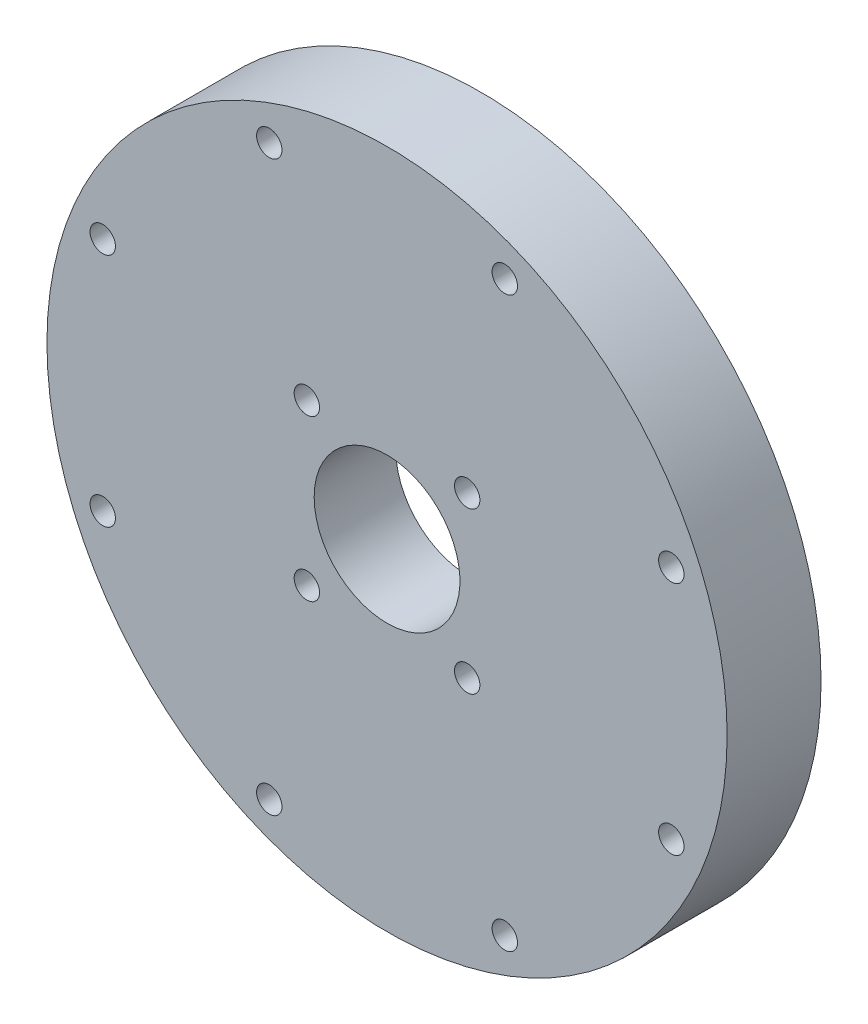
SolidWorks part; units mm, degrees
material "6061-T6 (SS)"
ref_plane "Front Plane" through (0, 0, 0) normal (0, 0, 1) x (1, 0, 0)
ref_plane "Top Plane" through (0, 0, 0) normal (0, 1, 0) x (1, 0, 0)
ref_plane "Right Plane" through (0, 0, 0) normal (1, 0, 0) x (0, 0, -1)
curve "Volute Curve"
  spline degree 3 poles (34.2618, 0, 0) (34.2648, 0.0718, 0) (34.2707, 0.2156, 0) (34.2778, 0.4312, 0) (34.2837, 0.647, 0) (34.2882, 0.8628, 0) (34.2914, 1.0787, 0) (34.2932, 1.2947, 0) (34.2937, 1.5108, 0) (34.2929, 1.7269, 0) (34.2907, 1.9431, 0) (34.2871, 2.1593, 0) (34.2822, 2.3756, 0) (34.2759, 2.5919, 0) (34.2683, 2.8082, 0) (34.2593, 3.0245, 0) (34.2489, 3.2407, 0) (34.2372, 3.457, 0) (34.2242, 3.6733, 0) (34.2098, 3.8895, 0) (34.194, 4.1058, 0) (34.1768, 4.3219, 0) (34.1583, 4.538, 0) (34.1385, 4.7541, 0) (34.1173, 4.9701, 0) (34.0947, 5.186, 0) (34.0708, 5.4018, 0) (34.0454, 5.6175, 0) (34.0188, 5.8331, 0) (33.9908, 6.0486, 0) (33.9614, 6.264, 0) (33.9306, 6.4793, 0) (33.8985, 6.6944, 0) (33.8651, 6.9094, 0) (33.8303, 7.1242, 0) (33.7941, 7.3388, 0) (33.7566, 7.5533, 0) (33.7177, 7.7676, 0) (33.6774, 7.9817, 0) (33.6358, 8.1956, 0) (33.5929, 8.4093, 0) (33.5486, 8.6228, 0) (33.5029, 8.8361, 0) (33.4559, 9.0491, 0) (33.4076, 9.2619, 0) (33.3579, 9.4745, 0) (33.3068, 9.6868, 0) (33.2544, 9.8988, 0) (33.2006, 10.1105, 0) (33.1456, 10.322, 0) (33.0891, 10.5332, 0) (33.0313, 10.744, 0) (32.9722, 10.9546, 0) (32.9118, 11.1648, 0) (32.85, 11.3748, 0) (32.7869, 11.5843, 0) (32.7224, 11.7936, 0) (32.6566, 12.0025, 0) (32.5895, 12.211, 0) (32.521, 12.4192, 0) (32.4513, 12.627, 0) (32.3802, 12.8344, 0) (32.3077, 13.0414, 0) (32.234, 13.248, 0) (32.1589, 13.4542, 0) (32.0826, 13.6599, 0) (32.0049, 13.8653, 0) (31.9259, 14.0702, 0) (31.8456, 14.2747, 0) (31.764, 14.4787, 0) (31.6811, 14.6823, 0) (31.5968, 14.8854, 0) (31.5113, 15.088, 0) (31.4245, 15.2901, 0) (31.3364, 15.4917, 0) (31.247, 15.6929, 0) (31.1563, 15.8935, 0) (31.0644, 16.0936, 0) (30.9711, 16.2932, 0) (30.8766, 16.4922, 0) (30.7808, 16.6907, 0) (30.6837, 16.8886, 0) (30.5854, 17.086, 0) (30.4858, 17.2829, 0) (30.3849, 17.4791, 0) (30.2828, 17.6748, 0) (30.1794, 17.8698, 0) (30.0747, 18.0643, 0) (29.9688, 18.2582, 0) (29.8617, 18.4514, 0) (29.7533, 18.644, 0) (29.6437, 18.836, 0) (29.5328, 19.0274, 0) (29.4208, 19.2181, 0) (29.3074, 19.4081, 0) (29.1929, 19.5975, 0) (29.0771, 19.7862, 0) (28.9601, 19.9742, 0) (28.842, 20.1616, 0) (28.7226, 20.3482, 0) (28.602, 20.5342, 0) (28.4801, 20.7194, 0) (28.3571, 20.904, 0) (28.233, 21.0877, 0) (28.1076, 21.2708, 0) (27.981, 21.4531, 0) (27.8533, 21.6347, 0) (27.7243, 21.8155, 0) (27.5942, 21.9956, 0) (27.463, 22.1748, 0) (27.3306, 22.3533, 0) (27.197, 22.531, 0) (27.0623, 22.708, 0) (26.9264, 22.8841, 0) (26.7894, 23.0594, 0) (26.6512, 23.2339, 0) (26.5119, 23.4075, 0) (26.3715, 23.5804, 0) (26.23, 23.7524, 0) (26.0873, 23.9235, 0) (25.9435, 24.0938, 0) (25.7987, 24.2632, 0) (25.6527, 24.4318, 0) (25.5056, 24.5995, 0) (25.3574, 24.7663, 0) (25.2082, 24.9322, 0) (25.0578, 25.0973, 0) (24.9064, 25.2614, 0) (24.7539, 25.4246, 0) (24.6003, 25.5869, 0) (24.4457, 25.7483, 0) (24.29, 25.9087, 0) (24.1333, 26.0682, 0) (23.9755, 26.2268, 0) (23.8167, 26.3844, 0) (23.6569, 26.541, 0) (23.496, 26.6967, 0) (23.3341, 26.8514, 0) (23.1712, 27.0051, 0) (23.0073, 27.1579, 0) (22.8424, 27.3096, 0) (22.6765, 27.4604, 0) (22.5096, 27.6101, 0) (22.3417, 27.7589, 0) (22.1728, 27.9066, 0) (22.003, 28.0533, 0) (21.8322, 28.199, 0) (21.6604, 28.3436, 0) (21.4877, 28.4872, 0) (21.314, 28.6297, 0) (21.1394, 28.7712, 0) (20.9639, 28.9116, 0) (20.7874, 29.051, 0) (20.61, 29.1892, 0) (20.4317, 29.3264, 0) (20.2524, 29.4626, 0) (20.0723, 29.5976, 0) (19.8913, 29.7315, 0) (19.7094, 29.8643, 0) (19.5266, 29.996, 0) (19.3429, 30.1266, 0) (19.1584, 30.2561, 0) (18.973, 30.3844, 0) (18.7867, 30.5116, 0) (18.5996, 30.6377, 0) (18.4117, 30.7626, 0) (18.2229, 30.8864, 0) (18.0333, 31.009, 0) (17.8429, 31.1304, 0) (17.6516, 31.2507, 0) (17.4596, 31.3698, 0) (17.2667, 31.4878, 0) (17.0731, 31.6045, 0) (16.8786, 31.7201, 0) (16.6834, 31.8344, 0) (16.4875, 31.9476, 0) (16.2907, 32.0596, 0) (16.0932, 32.1703, 0) (15.895, 32.2799, 0) (15.696, 32.3882, 0) (15.4963, 32.4953, 0) (15.2959, 32.6012, 0) (15.0947, 32.7058, 0) (14.8929, 32.8092, 0) (14.6903, 32.9114, 0) (14.487, 33.0123, 0) (14.2831, 33.1119, 0) (14.0784, 33.2103, 0) (13.8731, 33.3075, 0) (13.6672, 33.4033, 0) (13.4606, 33.4979, 0) (13.2533, 33.5912, 0) (13.0454, 33.6833, 0) (12.8368, 33.774, 0) (12.6277, 33.8635, 0) (12.4179, 33.9517, 0) (12.2075, 34.0385, 0) (11.9965, 34.1241, 0) (11.7849, 34.2084, 0) (11.5727, 34.2913, 0) (11.36, 34.373, 0) (11.1467, 34.4533, 0) (10.9328, 34.5323, 0) (10.7183, 34.61, 0) (10.5034, 34.6863, 0) (10.2879, 34.7613, 0) (10.0718, 34.835, 0) (9.8553, 34.9074, 0) (9.6382, 34.9783, 0) (9.4206, 35.048, 0) (9.2025, 35.1163, 0) (8.984, 35.1832, 0) (8.765, 35.2488, 0) (8.5455, 35.313, 0) (8.3255, 35.3759, 0) (8.1051, 35.4374, 0) (7.8842, 35.4975, 0) (7.6629, 35.5562, 0) (7.4412, 35.6136, 0) (7.2191, 35.6696, 0) (6.9965, 35.7242, 0) (6.7736, 35.7774, 0) (6.5503, 35.8292, 0) (6.3265, 35.8796, 0) (6.1024, 35.9287, 0) (5.878, 35.9763, 0) (5.6532, 36.0225, 0) (5.428, 36.0674, 0) (5.2025, 36.1108, 0) (4.9766, 36.1528, 0) (4.7505, 36.1934, 0) (4.524, 36.2326, 0) (4.2972, 36.2704, 0) (4.0701, 36.3067, 0) (3.8428, 36.3417, 0) (3.6151, 36.3752, 0) (3.3872, 36.4073, 0) (3.159, 36.438, 0) (2.9306, 36.4672, 0) (2.7019, 36.495, 0) (2.473, 36.5214, 0) (2.2439, 36.5463, 0) (2.0146, 36.5699, 0) (1.785, 36.5919, 0) (1.5553, 36.6126, 0) (1.3253, 36.6318, 0) (1.0952, 36.6495, 0) (0.8649, 36.6658, 0) (0.6345, 36.6807, 0) (0.4039, 36.6941, 0) (0.1731, 36.706, 0) (-0.0577, 36.7166, 0) (-0.2887, 36.7256, 0) (-0.5199, 36.7332, 0) (-0.7511, 36.7394, 0) (-0.9824, 36.7441, 0) (-1.2138, 36.7474, 0) (-1.4453, 36.7492, 0) (-1.6769, 36.7495, 0) (-1.9085, 36.7484, 0) (-2.1402, 36.7458, 0) (-2.3719, 36.7418, 0) (-2.6037, 36.7363, 0) (-2.8355, 36.7293, 0) (-3.0673, 36.7209, 0) (-3.2991, 36.711, 0) (-3.5309, 36.6997, 0) (-3.7627, 36.6869, 0) (-3.9944, 36.6726, 0) (-4.2262, 36.6569, 0) (-4.4579, 36.6397, 0) (-4.6895, 36.6211, 0) (-4.9211, 36.6009, 0) (-5.1526, 36.5794, 0) (-5.3841, 36.5563, 0) (-5.6154, 36.5318, 0) (-5.8467, 36.5059, 0) (-6.0779, 36.4784, 0) (-6.3089, 36.4495, 0) (-6.5399, 36.4192, 0) (-6.7706, 36.3874, 0) (-7.0013, 36.3541, 0) (-7.2318, 36.3194, 0) (-7.4621, 36.2832, 0) (-7.6923, 36.2455, 0) (-7.9223, 36.2064, 0) (-8.1521, 36.1658, 0) (-8.3817, 36.1238, 0) (-8.6111, 36.0803, 0) (-8.8403, 36.0354, 0) (-9.0693, 35.989, 0) (-9.298, 35.9411, 0) (-9.5265, 35.8918, 0) (-9.7548, 35.8411, 0) (-9.9827, 35.7889, 0) (-10.2105, 35.7352, 0) (-10.4379, 35.6802, 0) (-10.665, 35.6236, 0) (-10.8919, 35.5656, 0) (-11.1184, 35.5062, 0) (-11.3446, 35.4453, 0) (-11.5705, 35.383, 0) (-11.7961, 35.3193, 0) (-12.0213, 35.2541, 0) (-12.2461, 35.1875, 0) (-12.4706, 35.1194, 0) (-12.6948, 35.0499, 0) (-12.9185, 34.979, 0) (-13.1419, 34.9067, 0) (-13.3648, 34.8329, 0) (-13.5874, 34.7578, 0) (-13.8095, 34.6812, 0) (-14.0312, 34.6031, 0) (-14.2525, 34.5237, 0) (-14.4734, 34.4429, 0) (-14.6937, 34.3606, 0) (-14.9137, 34.2769, 0) (-15.1331, 34.1918, 0) (-15.3521, 34.1054, 0) (-15.5706, 34.0175, 0) (-15.7885, 33.9282, 0) (-16.006, 33.8375, 0) (-16.223, 33.7455, 0) (-16.4394, 33.652, 0) (-16.6553, 33.5572, 0) (-16.8707, 33.461, 0) (-17.0855, 33.3634, 0) (-17.2997, 33.2644, 0) (-17.5134, 33.164, 0) (-17.7265, 33.0623, 0) (-17.939, 32.9592, 0) (-18.151, 32.8548, 0) (-18.3623, 32.7489, 0) (-18.573, 32.6418, 0) (-18.7831, 32.5332, 0) (-18.9925, 32.4234, 0) (-19.2014, 32.3121, 0) (-19.4095, 32.1996, 0) (-19.6171, 32.0857, 0) (-19.8239, 31.9704, 0) (-20.0301, 31.8538, 0) (-20.2356, 31.7359, 0) (-20.4404, 31.6167, 0) (-20.6445, 31.4962, 0) (-20.8479, 31.3743, 0) (-21.0506, 31.2511, 0) (-21.2526, 31.1267, 0) (-21.4538, 31.0009, 0) (-21.6543, 30.8738, 0) (-21.854, 30.7454, 0) (-22.053, 30.6158, 0) (-22.2512, 30.4848, 0) (-22.4487, 30.3526, 0) (-22.6453, 30.2191, 0) (-22.8412, 30.0843, 0) (-23.0363, 29.9482, 0) (-23.2305, 29.8109, 0) (-23.424, 29.6723, 0) (-23.6166, 29.5325, 0) (-23.8084, 29.3915, 0) (-23.9994, 29.2491, 0) (-24.1895, 29.1056, 0) (-24.3787, 28.9608, 0) (-24.5671, 28.8148, 0) (-24.7546, 28.6676, 0) (-24.9413, 28.5191, 0) (-25.127, 28.3694, 0) (-25.3119, 28.2186, 0) (-25.4958, 28.0665, 0) (-25.6789, 27.9132, 0) (-25.861, 27.7587, 0) (-26.0422, 27.6031, 0) (-26.2224, 27.4463, 0) (-26.4018, 27.2882, 0) (-26.5801, 27.1291, 0) (-26.7576, 26.9687, 0) (-26.934, 26.8072, 0) (-27.1095, 26.6446, 0) (-27.284, 26.4808, 0) (-27.4575, 26.3159, 0) (-27.63, 26.1498, 0) (-27.8015, 25.9826, 0) (-27.972, 25.8143, 0) (-28.1415, 25.6448, 0) (-28.31, 25.4743, 0) (-28.4774, 25.3027, 0) (-28.6438, 25.1299, 0) (-28.8092, 24.9561, 0) (-28.9735, 24.7811, 0) (-29.1367, 24.6051, 0) (-29.2989, 24.4281, 0) (-29.46, 24.2499, 0) (-29.62, 24.0707, 0) (-29.7789, 23.8905, 0) (-29.9368, 23.7092, 0) (-30.0935, 23.5268, 0) (-30.2491, 23.3435, 0) (-30.4036, 23.1591, 0) (-30.557, 22.9737, 0) (-30.7093, 22.7872, 0) (-30.8604, 22.5998, 0) (-31.0104, 22.4114, 0) (-31.1592, 22.2219, 0) (-31.3069, 22.0315, 0) (-31.4534, 21.8402, 0) (-31.5988, 21.6478, 0) (-31.7429, 21.4545, 0) (-31.8859, 21.2602, 0) (-32.0277, 21.065, 0) (-32.1684, 20.8688, 0) (-32.3078, 20.6717, 0) (-32.446, 20.4737, 0) (-32.583, 20.2747, 0) (-32.7188, 20.0748, 0) (-32.8533, 19.8741, 0) (-32.9866, 19.6724, 0) (-33.1187, 19.4698, 0) (-33.2496, 19.2664, 0) (-33.3792, 19.0621, 0) (-33.5075, 18.8569, 0) (-33.6346, 18.6509, 0) (-33.7604, 18.444, 0) (-33.885, 18.2362, 0) (-34.0082, 18.0276, 0) (-34.1302, 17.8182, 0) (-34.2509, 17.608, 0) (-34.3703, 17.397, 0) (-34.4884, 17.1851, 0) (-34.6052, 16.9725, 0) (-34.7207, 16.7591, 0) (-34.8349, 16.5449, 0) (-34.9478, 16.3299, 0) (-35.0593, 16.1141, 0) (-35.1695, 15.8976, 0) (-35.2784, 15.6804, 0) (-35.3859, 15.4624, 0) (-35.4921, 15.2436, 0) (-35.597, 15.0242, 0) (-35.7004, 14.804, 0) (-35.8026, 14.5832, 0) (-35.9033, 14.3616, 0) (-36.0027, 14.1393, 0) (-36.1007, 13.9164, 0) (-36.1973, 13.6928, 0) (-36.2926, 13.4685, 0) (-36.3864, 13.2436, 0) (-36.4789, 13.018, 0) (-36.57, 12.7918, 0) (-36.6596, 12.5649, 0) (-36.7479, 12.3374, 0) (-36.8348, 12.1094, 0) (-36.9202, 11.8807, 0) (-37.0042, 11.6514, 0) (-37.0868, 11.4215, 0) (-37.168, 11.1911, 0) (-37.2477, 10.96, 0) (-37.326, 10.7285, 0) (-37.4029, 10.4963, 0) (-37.4783, 10.2637, 0) (-37.5523, 10.0305, 0) (-37.6248, 9.7967, 0) (-37.6959, 9.5625, 0) (-37.7655, 9.3277, 0) (-37.8337, 9.0925, 0) (-37.9004, 8.8568, 0) (-37.9656, 8.6205, 0) (-38.0293, 8.3839, 0) (-38.0916, 8.1467, 0) (-38.1524, 7.9091, 0) (-38.2117, 7.6711, 0) (-38.2696, 7.4326, 0) (-38.3259, 7.1937, 0) (-38.3808, 6.9544, 0) (-38.4342, 6.7147, 0) (-38.486, 6.4746, 0) (-38.5364, 6.2341, 0) (-38.5853, 5.9932, 0) (-38.6326, 5.7519, 0) (-38.6785, 5.5103, 0) (-38.7229, 5.2684, 0) (-38.7657, 5.0261, 0) (-38.807, 4.7835, 0) (-38.8468, 4.5405, 0) (-38.8851, 4.2973, 0) (-38.9219, 4.0537, 0) (-38.9571, 3.8099, 0) (-38.9908, 3.5657, 0) (-39.023, 3.3213, 0) (-39.0537, 3.0767, 0) (-39.0828, 2.8317, 0) (-39.1104, 2.5866, 0) (-39.1364, 2.3412, 0) (-39.1609, 2.0955, 0) (-39.1839, 1.8497, 0) (-39.2053, 1.6037, 0) (-39.2252, 1.3574, 0) (-39.2435, 1.111, 0) (-39.2603, 0.8644, 0) (-39.2756, 0.6176, 0) (-39.2893, 0.3707, 0) (-39.3014, 0.1236, 0) (-39.312, -0.1236, 0) (-39.321, -0.371, 0) (-39.3285, -0.6185, 0) (-39.3344, -0.866, 0) (-39.3388, -1.1137, 0) (-39.3416, -1.3615, 0) (-39.3428, -1.6093, 0) (-39.3425, -1.8572, 0) (-39.3406, -2.1052, 0) (-39.3372, -2.3532, 0) (-39.3322, -2.6013, 0) (-39.3257, -2.8494, 0) (-39.3175, -3.0975, 0) (-39.3078, -3.3456, 0) (-39.2966, -3.5937, 0) (-39.2838, -3.8418, 0) (-39.2694, -4.0899, 0) (-39.2534, -4.338, 0) (-39.2359, -4.586, 0) (-39.2168, -4.834, 0) (-39.1962, -5.0819, 0) (-39.174, -5.3298, 0) (-39.1502, -5.5776, 0) (-39.1248, -5.8252, 0) (-39.0979, -6.0728, 0) (-39.0694, -6.3203, 0) (-39.0394, -6.5677, 0) (-39.0078, -6.8149, 0) (-38.9746, -7.062, 0) (-38.9399, -7.309, 0) (-38.9036, -7.5558, 0) (-38.8657, -7.8024, 0) (-38.8263, -8.0488, 0) (-38.7853, -8.2951, 0) (-38.7427, -8.5411, 0) (-38.6986, -8.787, 0) (-38.653, -9.0326, 0) (-38.6057, -9.2781, 0) (-38.557, -9.5232, 0) (-38.5066, -9.7682, 0) (-38.4547, -10.0128, 0) (-38.4013, -10.2572, 0) (-38.3463, -10.5014, 0) (-38.2897, -10.7452, 0) (-38.2316, -10.9888, 0) (-38.172, -11.232, 0) (-38.1108, -11.475, 0) (-38.048, -11.7176, 0) (-37.9838, -11.9598, 0) (-37.9179, -12.2018, 0) (-37.8506, -12.4433, 0) (-37.7817, -12.6845, 0) (-37.7112, -12.9254, 0) (-37.6393, -13.1658, 0) (-37.5658, -13.4059, 0) (-37.4907, -13.6455, 0) (-37.4142, -13.8848, 0) (-37.3361, -14.1236, 0) (-37.2565, -14.362, 0) (-37.1753, -14.5999, 0) (-37.0927, -14.8374, 0) (-37.0085, -15.0744, 0) (-36.9228, -15.311, 0) (-36.8357, -15.547, 0) (-36.747, -15.7826, 0) (-36.6568, -16.0177, 0) (-36.5651, -16.2523, 0) (-36.4719, -16.4863, 0) (-36.3772, -16.7199, 0) (-36.281, -16.9528, 0) (-36.1833, -17.1853, 0) (-36.0841, -17.4172, 0) (-35.9834, -17.6485, 0) (-35.8813, -17.8792, 0) (-35.7777, -18.1094, 0) (-35.6726, -18.3389, 0) (-35.566, -18.5679, 0) (-35.458, -18.7962, 0) (-35.3485, -19.0239, 0) (-35.2376, -19.251, 0) (-35.1251, -19.4774, 0) (-35.0113, -19.7032, 0) (-34.896, -19.9283, 0) (-34.7792, -20.1528, 0) (-34.661, -20.3765, 0) (-34.5414, -20.5996, 0) (-34.4203, -20.822, 0) (-34.2978, -21.0437, 0) (-34.1738, -21.2646, 0) (-34.0485, -21.4849, 0) (-33.9217, -21.7044, 0) (-33.7935, -21.9231, 0) (-33.6639, -22.1411, 0) (-33.5329, -22.3584, 0) (-33.4005, -22.5748, 0) (-33.2667, -22.7905, 0) (-33.1315, -23.0054, 0) (-32.995, -23.2195, 0) (-32.857, -23.4328, 0) (-32.7177, -23.6453, 0) (-32.577, -23.8569, 0) (-32.4349, -24.0677, 0) (-32.2915, -24.2777, 0) (-32.1467, -24.4868, 0) (-32.0006, -24.6951, 0) (-31.8531, -24.9025, 0) (-31.7042, -25.109, 0) (-31.5541, -25.3146, 0) (-31.4026, -25.5194, 0) (-31.2497, -25.7232, 0) (-31.0956, -25.9261, 0) (-30.9401, -26.1281, 0) (-30.7833, -26.3292, 0) (-30.6253, -26.5293, 0) (-30.4659, -26.7285, 0) (-30.3052, -26.9267, 0) (-30.1433, -27.124, 0) (-29.98, -27.3203, 0) (-29.8155, -27.5156, 0) (-29.6497, -27.7099, 0) (-29.4827, -27.9032, 0) (-29.3144, -28.0956, 0) (-29.1448, -28.2869, 0) (-28.974, -28.4772, 0) (-28.8019, -28.6664, 0) (-28.6287, -28.8546, 0) (-28.4542, -29.0418, 0) (-28.2784, -29.2279, 0) (-28.1015, -29.413, 0) (-27.9233, -29.597, 0) (-27.744, -29.7799, 0) (-27.5634, -29.9618, 0) (-27.3817, -30.1425, 0) (-27.1987, -30.3221, 0) (-27.0146, -30.5007, 0) (-26.8294, -30.6781, 0) (-26.6429, -30.8544, 0) (-26.4554, -31.0296, 0) (-26.2666, -31.2036, 0) (-26.0767, -31.3765, 0) (-25.8857, -31.5482, 0) (-25.6936, -31.7188, 0) (-25.5003, -31.8882, 0) (-25.306, -32.0564, 0) (-25.1105, -32.2234, 0) (-24.9139, -32.3893, 0) (-24.7162, -32.5539, 0) (-24.5175, -32.7174, 0) (-24.3176, -32.8796, 0) (-24.1167, -33.0406, 0) (-23.9147, -33.2004, 0) (-23.7117, -33.359, 0) (-23.5076, -33.5163, 0) (-23.3025, -33.6724, 0) (-23.0964, -33.8272, 0) (-22.8892, -33.9807, 0) (-22.681, -34.133, 0) (-22.4718, -34.2841, 0) (-22.2616, -34.4338, 0) (-22.0504, -34.5822, 0) (-21.8382, -34.7294, 0) (-21.6251, -34.8752, 0) (-21.4109, -35.0198, 0) (-21.1959, -35.163, 0) (-20.9798, -35.3049, 0) (-20.7628, -35.4455, 0) (-20.5449, -35.5848, 0) (-20.326, -35.7227, 0) (-20.1062, -35.8593, 0) (-19.8855, -35.9945, 0) (-19.6639, -36.1284, 0) (-19.4414, -36.2609, 0) (-19.2181, -36.392, 0) (-18.9938, -36.5218, 0) (-18.7686, -36.6502, 0) (-18.5426, -36.7772, 0) (-18.3158, -36.9028, 0) (-18.0881, -37.027, 0) (-17.8595, -37.1498, 0) (-17.6302, -37.2712, 0) (-17.4, -37.3911, 0) (-17.169, -37.5097, 0) (-16.9372, -37.6268, 0) (-16.7046, -37.7425, 0) (-16.4712, -37.8568, 0) (-16.237, -37.9696, 0) (-16.0021, -38.081, 0) (-15.7664, -38.1909, 0) (-15.53, -38.2994, 0) (-15.2928, -38.4064, 0) (-15.0549, -38.5119, 0) (-14.8163, -38.616, 0) (-14.577, -38.7185, 0) (-14.3369, -38.8196, 0) (-14.0962, -38.9192, 0) (-13.8547, -39.0174, 0) (-13.6126, -39.114, 0) (-13.3699, -39.2091, 0) (-13.1265, -39.3027, 0) (-12.8824, -39.3949, 0) (-12.6377, -39.4854, 0) (-12.3923, -39.5745, 0) (-12.1464, -39.6621, 0) (-11.8998, -39.7481, 0) (-11.6526, -39.8326, 0) (-11.4048, -39.9155, 0) (-11.1565, -39.997, 0) (-10.9076, -40.0768, 0) (-10.6581, -40.1552, 0) (-10.408, -40.2319, 0) (-10.1575, -40.3071, 0) (-9.9063, -40.3808, 0) (-9.6547, -40.4529, 0) (-9.4025, -40.5234, 0) (-9.1499, -40.5924, 0) (-8.8967, -40.6598, 0) (-8.6431, -40.7256, 0) (-8.389, -40.7898, 0) (-8.1344, -40.8524, 0) (-7.8793, -40.9135, 0) (-7.6239, -40.9729, 0) (-7.3679, -41.0308, 0) (-7.1116, -41.087, 0) (-6.8548, -41.1417, 0) (-6.5977, -41.1948, 0) (-6.3401, -41.2462, 0) (-6.0821, -41.2961, 0) (-5.8238, -41.3443, 0) (-5.5651, -41.3909, 0) (-5.3061, -41.4359, 0) (-5.0467, -41.4793, 0) (-4.7869, -41.5211, 0) (-4.5269, -41.5612, 0) (-4.2665, -41.5997, 0) (-4.0058, -41.6366, 0) (-3.7449, -41.6718, 0) (-3.4836, -41.7054, 0) (-3.2221, -41.7374, 0) (-2.9603, -41.7677, 0) (-2.6982, -41.7964, 0) (-2.4359, -41.8234, 0) (-2.1734, -41.8488, 0) (-1.9106, -41.8726, 0) (-1.6477, -41.8947, 0) (-1.3845, -41.9151, 0) (-1.1212, -41.9339, 0) (-0.8576, -41.9511, 0) (-0.5939, -41.9666, 0) (-0.33, -41.9804, 0) (-0.066, -41.9926, 0) (0.1981, -42.0031, 0) (0.4624, -42.012, 0) (0.7268, -42.0192, 0) (0.9914, -42.0247, 0) (1.256, -42.0286, 0) (1.5207, -42.0308, 0) (1.7855, -42.0313, 0) (2.0503, -42.0302, 0) (2.3152, -42.0274, 0) (2.5802, -42.0229, 0) (2.8452, -42.0168, 0) (3.1102, -42.0089, 0) (3.3752, -41.9995, 0) (3.6403, -41.9883, 0) (3.9053, -41.9755, 0) (4.1703, -41.961, 0) (4.4353, -41.9448, 0) (4.7002, -41.927, 0) (4.9651, -41.9075, 0) (5.2299, -41.8863, 0) (5.4947, -41.8634, 0) (5.7594, -41.8389, 0) (6.024, -41.8127, 0) (6.2885, -41.7848, 0) (6.5528, -41.7553, 0) (6.8171, -41.7241, 0) (7.0812, -41.6912, 0) (7.3452, -41.6566, 0) (7.609, -41.6204, 0) (7.8727, -41.5825, 0) (8.1362, -41.5429, 0) (8.3995, -41.5017, 0) (8.6626, -41.4588, 0) (8.9254, -41.4142, 0) (9.1881, -41.3679, 0) (9.4506, -41.32, 0) (9.7128, -41.2705, 0) (9.9747, -41.2192, 0) (10.2364, -41.1663, 0) (10.4979, -41.1118, 0) (10.759, -41.0556, 0) (11.0199, -40.9977, 0) (11.2804, -40.9382, 0) (11.5407, -40.877, 0) (11.8006, -40.8141, 0) (12.0602, -40.7496, 0) (12.3194, -40.6835, 0) (12.5783, -40.6157, 0) (12.8368, -40.5463, 0) (13.0949, -40.4752, 0) (13.3527, -40.4025, 0) (13.6101, -40.3281, 0) (13.867, -40.2521, 0) (14.1235, -40.1745, 0) (14.3797, -40.0952, 0) (14.6353, -40.0143, 0) (14.8905, -39.9318, 0) (15.1453, -39.8476, 0) (15.3996, -39.7618, 0) (15.6534, -39.6744, 0) (15.9067, -39.5854, 0) (16.1596, -39.4948, 0) (16.4119, -39.4025, 0) (16.6637, -39.3087, 0) (16.9149, -39.2132, 0) (17.1657, -39.1161, 0) (17.4158, -39.0174, 0) (17.6654, -38.9172, 0) (17.9145, -38.8153, 0) (18.1629, -38.7118, 0) (18.4108, -38.6068, 0) (18.658, -38.5001, 0) (18.9047, -38.3919, 0) (19.1507, -38.2821, 0) (19.3961, -38.1707, 0) (19.6408, -38.0578, 0) (19.8849, -37.9433, 0) (20.1283, -37.8272, 0) (20.3711, -37.7095, 0) (20.6132, -37.5904, 0) (20.8546, -37.4696, 0) (21.0952, -37.3473, 0) (21.3352, -37.2235, 0) (21.5744, -37.0981, 0) (21.8129, -36.9712, 0) (22.0507, -36.8427, 0) (22.2877, -36.7127, 0) (22.524, -36.5812, 0) (22.7594, -36.4482, 0) (22.9941, -36.3137, 0) (23.228, -36.1776, 0) (23.4611, -36.0401, 0) (23.6934, -35.901, 0) (23.9249, -35.7605, 0) (24.1556, -35.6184, 0) (24.3854, -35.4749, 0) (24.6143, -35.3299, 0) (24.8424, -35.1834, 0) (25.0696, -35.0355, 0) (25.296, -34.8861, 0) (25.5214, -34.7352, 0) (25.746, -34.5828, 0) (25.9696, -34.4291, 0) (26.1924, -34.2738, 0) (26.4142, -34.1172, 0) (26.6351, -33.9591, 0) (26.855, -33.7995, 0) (27.074, -33.6386, 0) (27.292, -33.4762, 0) (27.5091, -33.3124, 0) (27.7252, -33.1472, 0) (27.9402, -32.9807, 0) (28.1543, -32.8127, 0) (28.3674, -32.6433, 0) (28.5795, -32.4726, 0) (28.7905, -32.3004, 0) (29.0005, -32.127, 0) (29.2095, -31.9521, 0) (29.4174, -31.7759, 0) (29.6242, -31.5983, 0) (29.83, -31.4194, 0) (30.0347, -31.2392, 0) (30.2383, -31.0576, 0) (30.4408, -30.8747, 0) (30.6422, -30.6905, 0) (30.8426, -30.5049, 0) (31.0417, -30.3181, 0) (31.2398, -30.1299, 0) (31.4367, -29.9405, 0) (31.6325, -29.7498, 0) (31.8271, -29.5578, 0) (32.0205, -29.3645, 0) (32.2128, -29.17, 0) (32.4039, -28.9742, 0) (32.5938, -28.7772, 0) (32.7825, -28.5789, 0) (32.97, -28.3794, 0) (33.1563, -28.1787, 0) (33.3414, -27.9767, 0) (33.5252, -27.7736, 0) (33.7079, -27.5692, 0) (33.8892, -27.3636, 0) (34.0693, -27.1569, 0) (34.2482, -26.9489, 0) (34.4258, -26.7398, 0) (34.6021, -26.5295, 0) (34.7771, -26.3181, 0) (34.9509, -26.1055, 0) (35.1233, -25.8917, 0) (35.2944, -25.6768, 0) (35.4643, -25.4608, 0) (35.6328, -25.2437, 0) (35.7999, -25.0255, 0) (35.9658, -24.8061, 0) (36.1303, -24.5857, 0) (36.2934, -24.3641, 0) (36.4552, -24.1415, 0) (36.6157, -23.9179, 0) (36.7747, -23.6931, 0) (36.9324, -23.4673, 0) (37.0887, -23.2405, 0) (37.2436, -23.0126, 0) (37.3971, -22.7837, 0) (37.5492, -22.5538, 0) (37.6999, -22.3228, 0) (37.8491, -22.0909, 0) (37.997, -21.858, 0) (38.1434, -21.624, 0) (38.2884, -21.3891, 0) (38.4319, -21.1533, 0) (38.574, -20.9165, 0) (38.7146, -20.6787, 0) (38.8537, -20.44, 0) (38.9914, -20.2003, 0) (39.1276, -19.9598, 0) (39.2623, -19.7183, 0) (39.3956, -19.4759, 0) (39.5273, -19.2326, 0) (39.6575, -18.9884, 0) (39.7863, -18.7434, 0) (39.9135, -18.4975, 0) (40.0392, -18.2507, 0) (40.1633, -18.0031, 0) (40.286, -17.7546, 0) (40.4071, -17.5053, 0) (40.5267, -17.2552, 0) (40.6447, -17.0043, 0) (40.7611, -16.7525, 0) (40.876, -16.5, 0) (40.9894, -16.2467, 0) (41.1012, -15.9927, 0) (41.2114, -15.7378, 0) (41.32, -15.4822, 0) (41.427, -15.2259, 0) (41.5325, -14.9688, 0) (41.6363, -14.711, 0) (41.7386, -14.4525, 0) (41.8392, -14.1933, 0) (41.9383, -13.9334, 0) (42.0357, -13.6728, 0) (42.1315, -13.4116, 0) (42.2257, -13.1496, 0) (42.3182, -12.8871, 0) (42.4092, -12.6238, 0) (42.4985, -12.36, 0) (42.5861, -12.0955, 0) (42.6721, -11.8304, 0) (42.7565, -11.5647, 0) (42.8392, -11.2984, 0) (42.9202, -11.0315, 0) (42.9996, -10.7641, 0) (43.0773, -10.4961, 0) (43.1534, -10.2275, 0) (43.2277, -9.9584, 0) (43.3004, -9.6888, 0) (43.3715, -9.4186, 0) (43.4408, -9.148, 0) (43.5084, -8.8768, 0) (43.5744, -8.6052, 0) (43.6386, -8.333, 0) (43.7012, -8.0604, 0) (43.7621, -7.7874, 0) (43.8212, -7.5139, 0) (43.8786, -7.24, 0) (43.9344, -6.9656, 0) (43.9884, -6.6908, 0) (44.0407, -6.4156, 0) (44.0913, -6.1401, 0) (44.1401, -5.8641, 0) (44.1872, -5.5878, 0) (44.2326, -5.3111, 0) (44.2763, -5.0341, 0) (44.3182, -4.7567, 0) (44.3584, -4.479, 0) (44.3969, -4.201, 0) (44.4336, -3.9226, 0) (44.4686, -3.644, 0) (44.5018, -3.3651, 0) (44.5333, -3.0859, 0) (44.563, -2.8065, 0) (44.591, -2.5268, 0) (44.6172, -2.2468, 0) (44.6416, -1.9667, 0) (44.6643, -1.6863, 0) (44.6853, -1.4057, 0) (44.7044, -1.1249, 0) (44.7219, -0.8439, 0) (44.7375, -0.5628, 0) (44.7515, -0.2815, 0) (44.7593, -0.0938, 0) (44.7632, 0, 0) knots 0 0 0 0 0.000871 0.001743 0.002614 0.003486 0.004358 0.005231 0.006103 0.006976 0.007849 0.008723 0.009596 0.01047 0.011344 0.012219 0.013093 0.013968 0.014843 0.015718 0.016594 0.017469 0.018345 0.019222 0.020098 0.020975 0.021852 0.022729 0.023606 0.024484 0.025362 0.02624 0.027119 0.027997 0.028876 0.029755 0.030635 0.031514 0.032394 0.033274 0.034154 0.035035 0.035916 0.036797 0.037678 0.03856 0.039442 0.040324 0.041206 0.042089 0.042971 0.043854 0.044738 0.045621 0.046505 0.047389 0.048273 0.049158 0.050042 0.050927 0.051813 0.052698 0.053584 0.05447 0.055356 0.056242 0.057129 0.058016 0.058903 0.059791 0.060678 0.061566 0.062454 0.063343 0.064232 0.06512 0.06601 0.066899 0.067789 0.068679 0.069569 0.070459 0.07135 0.072241 0.073132 0.074023 0.074915 0.075807 0.076699 0.077591 0.078484 0.079377 0.08027 0.081163 0.082057 0.082951 0.083845 0.084739 0.085634 0.086529 0.087424 0.088319 0.089215 0.090111 0.091007 0.091903 0.0928 0.093696 0.094594 0.095491 0.096388 0.097286 0.098184 0.099083 0.099981 0.10088 0.101779 0.102679 0.103578 0.104478 0.105378 0.106279 0.107179 0.10808 0.108981 0.109882 0.110784 0.111686 0.112588 0.11349 0.114393 0.115296 0.116199 0.117102 0.118006 0.11891 0.119814 0.120718 0.121623 0.122528 0.123433 0.124338 0.125244 0.12615 0.127056 0.127962 0.128869 0.129776 0.130683 0.13159 0.132498 0.133406 0.134314 0.135222 0.136131 0.13704 0.137949 0.138858 0.139768 0.140678 0.141588 0.142498 0.143409 0.14432 0.145231 0.146142 0.147054 0.147966 0.148878 0.149791 0.150703 0.151616 0.152529 0.153443 0.154357 0.155271 0.156185 0.157099 0.158014 0.158929 0.159844 0.16076 0.161675 0.162591 0.163508 0.164424 0.165341 0.166258 0.167175 0.168093 0.16901 0.169928 0.170847 0.171765 0.172684 0.173603 0.174522 0.175442 0.176362 0.177282 0.178202 0.179123 0.180044 0.180965 0.181886 0.182808 0.183729 0.184652 0.185574 0.186497 0.187419 0.188343 0.189266 0.19019 0.191113 0.192038 0.192962 0.193887 0.194812 0.195737 0.196662 0.197588 0.198514 0.19944 0.200367 0.201293 0.20222 0.203147 0.204075 0.205003 0.205931 0.206859 0.207787 0.208716 0.209645 0.210575 0.211504 0.212434 0.213364 0.214294 0.215225 0.216156 0.217087 0.218018 0.21895 0.219882 0.220814 0.221746 0.222679 0.223612 0.224545 0.225478 0.226412 0.227346 0.22828 0.229214 0.230149 0.231084 0.232019 0.232955 0.23389 0.234826 0.235763 0.236699 0.237636 0.238573 0.23951 0.240448 0.241386 0.242324 0.243262 0.244201 0.245139 0.246078 0.247018 0.247957 0.248897 0.249837 0.250778 0.251718 0.252659 0.253601 0.254542 0.255484 0.256426 0.257368 0.25831 0.259253 0.260196 0.261139 0.262083 0.263027 0.263971 0.264915 0.265859 0.266804 0.267749 0.268695 0.26964 0.270586 0.271532 0.272479 0.273425 0.274372 0.275319 0.276267 0.277214 0.278162 0.27911 0.280059 0.281008 0.281957 0.282906 0.283855 0.284805 0.285755 0.286705 0.287656 0.288607 0.289558 0.290509 0.291461 0.292413 0.293365 0.294317 0.29527 0.296223 0.297176 0.298129 0.299083 0.300037 0.300991 0.301946 0.3029 0.303855 0.30481 0.305766 0.306722 0.307678 0.308634 0.309591 0.310548 0.311505 0.312462 0.31342 0.314377 0.315336 0.316294 0.317253 0.318212 0.319171 0.32013 0.32109 0.32205 0.32301 0.323971 0.324931 0.325892 0.326854 0.327815 0.328777 0.329739 0.330702 0.331664 0.332627 0.33359 0.334554 0.335517 0.336481 0.337445 0.33841 0.339375 0.34034 0.341305 0.34227 0.343236 0.344202 0.345168 0.346135 0.347102 0.348069 0.349036 0.350004 0.350972 0.35194 0.352908 0.353877 0.354846 0.355815 0.356785 0.357754 0.358724 0.359695 0.360665 0.361636 0.362607 0.363578 0.36455 0.365522 0.366494 0.367466 0.368439 0.369412 0.370385 0.371358 0.372332 0.373306 0.37428 0.375255 0.37623 0.377205 0.37818 0.379156 0.380131 0.381107 0.382084 0.38306 0.384037 0.385015 0.385992 0.38697 0.387948 0.388926 0.389904 0.390883 0.391862 0.392841 0.393821 0.394801 0.395781 0.396761 0.397742 0.398723 0.399704 0.400685 0.401667 0.402649 0.403631 0.404614 0.405596 0.406579 0.407563 0.408546 0.40953 0.410514 0.411498 0.412483 0.413468 0.414453 0.415438 0.416424 0.41741 0.418396 0.419383 0.420369 0.421357 0.422344 0.423331 0.424319 0.425307 0.426296 0.427284 0.428273 0.429262 0.430252 0.431241 0.432231 0.433222 0.434212 0.435203 0.436194 0.437185 0.438177 0.439169 0.440161 0.441153 0.442146 0.443139 0.444132 0.445125 0.446119 0.447113 0.448107 0.449102 0.450096 0.451091 0.452087 0.453082 0.454078 0.455074 0.456071 0.457067 0.458064 0.459061 0.460059 0.461057 0.462055 0.463053 0.464051 0.46505 0.466049 0.467049 0.468048 0.469048 0.470048 0.471049 0.472049 0.47305 0.474052 0.475053 0.476055 0.477057 0.478059 0.479062 0.480065 0.481068 0.482071 0.483075 0.484079 0.485083 0.486087 0.487092 0.488097 0.489102 0.490108 0.491114 0.49212 0.493126 0.494133 0.49514 0.496147 0.497154 0.498162 0.49917 0.500178 0.501187 0.502196 0.503205 0.504214 0.505224 0.506233 0.507244 0.508254 0.509265 0.510276 0.511287 0.512298 0.51331 0.514322 0.515334 0.516347 0.51736 0.518373 0.519386 0.5204 0.521414 0.522428 0.523442 0.524457 0.525472 0.526488 0.527503 0.528519 0.529535 0.530551 0.531568 0.532585 0.533602 0.53462 0.535637 0.536655 0.537673 0.538692 0.539711 0.54073 0.541749 0.542769 0.543789 0.544809 0.545829 0.54685 0.547871 0.548892 0.549914 0.550936 0.551958 0.55298 0.554003 0.555026 0.556049 0.557072 0.558096 0.55912 0.560144 0.561169 0.562193 0.563218 0.564244 0.565269 0.566295 0.567321 0.568348 0.569375 0.570402 0.571429 0.572456 0.573484 0.574512 0.575541 0.576569 0.577598 0.578627 0.579657 0.580686 0.581716 0.582747 0.583777 0.584808 0.585839 0.58687 0.587902 0.588934 0.589966 0.590998 0.592031 0.593064 0.594097 0.595131 0.596165 0.597199 0.598233 0.599268 0.600303 0.601338 0.602373 0.603409 0.604445 0.605481 0.606518 0.607554 0.608592 0.609629 0.610667 0.611704 0.612743 0.613781 0.61482 0.615859 0.616898 0.617938 0.618977 0.620018 0.621058 0.622099 0.62314 0.624181 0.625222 0.626264 0.627306 0.628348 0.629391 0.630434 0.631477 0.63252 0.633564 0.634608 0.635652 0.636697 0.637741 0.638786 0.639832 0.640877 0.641923 0.642969 0.644016 0.645062 0.646109 0.647157 0.648204 0.649252 0.6503 0.651348 0.652397 0.653446 0.654495 0.655545 0.656594 0.657644 0.658695 0.659745 0.660796 0.661847 0.662898 0.66395 0.665002 0.666054 0.667107 0.668159 0.669212 0.670266 0.671319 0.672373 0.673427 0.674482 0.675536 0.676591 0.677647 0.678702 0.679758 0.680814 0.68187 0.682927 0.683984 0.685041 0.686099 0.687156 0.688214 0.689273 0.690331 0.69139 0.692449 0.693508 0.694568 0.695628 0.696688 0.697749 0.69881 0.699871 0.700932 0.701994 0.703055 0.704118 0.70518 0.706243 0.707306 0.708369 0.709433 0.710496 0.71156 0.712625 0.713689 0.714754 0.71582 0.716885 0.717951 0.719017 0.720083 0.72115 0.722217 0.723284 0.724351 0.725419 0.726487 0.727555 0.728624 0.729693 0.730762 0.731831 0.732901 0.733971 0.735041 0.736111 0.737182 0.738253 0.739324 0.740396 0.741468 0.74254 0.743612 0.744685 0.745758 0.746831 0.747905 0.748979 0.750053 0.751127 0.752202 0.753277 0.754352 0.755428 0.756503 0.757579 0.758656 0.759732 0.760809 0.761886 0.762964 0.764041 0.765119 0.766198 0.767276 0.768355 0.769434 0.770514 0.771593 0.772673 0.773754 0.774834 0.775915 0.776996 0.778077 0.779159 0.780241 0.781323 0.782405 0.783488 0.784571 0.785654 0.786738 0.787822 0.788906 0.789991 0.791075 0.79216 0.793245 0.794331 0.795417 0.796503 0.797589 0.798676 0.799763 0.80085 0.801938 0.803025 0.804113 0.805202 0.80629 0.807379 0.808468 0.809558 0.810648 0.811738 0.812828 0.813919 0.815009 0.816101 0.817192 0.818284 0.819376 0.820468 0.82156 0.822653 0.823746 0.82484 0.825933 0.827027 0.828122 0.829216 0.830311 0.831406 0.832501 0.833597 0.834693 0.835789 0.836885 0.837982 0.839079 0.840177 0.841274 0.842372 0.84347 0.844569 0.845667 0.846766 0.847866 0.848965 0.850065 0.851165 0.852266 0.853366 0.854467 0.855568 0.85667 0.857772 0.858874 0.859976 0.861079 0.862182 0.863285 0.864389 0.865492 0.866596 0.867701 0.868805 0.86991 0.871016 0.872121 0.873227 0.874333 0.875439 0.876546 0.877653 0.87876 0.879867 0.880975 0.882083 0.883191 0.8843 0.885409 0.886518 0.887627 0.888737 0.889847 0.890957 0.892068 0.893179 0.89429 0.895401 0.896513 0.897625 0.898737 0.89985 0.900962 0.902075 0.903189 0.904303 0.905416 0.906531 0.907645 0.90876 0.909875 0.91099 0.912106 0.913222 0.914338 0.915455 0.916571 0.917689 0.918806 0.919923 0.921041 0.92216 0.923278 0.924397 0.925516 0.926635 0.927755 0.928875 0.929995 0.931115 0.932236 0.933357 0.934478 0.9356 0.936722 0.937844 0.938966 0.940089 0.941212 0.942335 0.943459 0.944583 0.945707 0.946831 0.947956 0.949081 0.950206 0.951332 0.952458 0.953584 0.95471 0.955837 0.956964 0.958091 0.959219 0.960347 0.961475 0.962603 0.963732 0.964861 0.96599 0.96712 0.968249 0.96938 0.97051 0.971641 0.972772 0.973903 0.975034 0.976166 0.977298 0.978431 0.979563 0.980696 0.981829 0.982963 0.984097 0.985231 0.986365 0.9875 0.988635 0.98977 0.990906 0.992041 0.993178 0.994314 0.995451 0.996587 0.997725 0.998862 1 1 1 1
sketch "Sketch16" plane through (0, 0, 0) normal (0, 1, 0) x (1, 0, 0)
  line L0 (14.2875, -24.13) -> (66.675, -24.13)
  line L1 (66.675, -24.13) -> (66.675, 0)
  line L2 (66.675, 0) -> (14.2875, 0)
  line L3 (14.2875, 0) -> (14.2875, -24.13)
  line L8 (0, 0) -> (0, -24.13) construction
  dimension "D1" = 133.35
  dimension "D3" = 24.13
  dimension "D7" = 28.575
revolve "Main Body" add sketch "Sketch16" angle 360 about L8
sketch "Sketch18" plane through (0, 0, 0) normal (0, 0, -1) x (-1, 0, 0)
  arc A13 (-43.8192, -7.5219) -> (-38.9898, 0) centre (-37.6087, -6.198) cw construction
  arc A14 (-34.0631, 5.4663) -> (-38.9898, 0) centre (-40.3708, 6.198) cw construction
  arc A15 (-43.7695, -7.5113) -> (-38.9787, -0.0496) centre (-37.6087, -6.198) cw
  arc A16 (-34.0126, 5.4604) -> (-38.9787, -0.0496) centre (-40.3708, 6.198) cw
  arc A17 (-34.0126, 5.4604) -> (-38.9787, -0.0496) centre (-40.3708, 6.198) cw construction
  spline S0 degree 1 poles (-34.2111, 0.0021) (-44.7125, 0.0021) knots 0 0 1 1 construction
  spline S1 degree 3 poles (-4027.9688, -203.419) (-16.3766, -34.1825) (-33.6935, -17.228) (-34.2778, 0.4312) (-34.2837, 0.647) (-34.2927, 1.0788) (-34.2982, 2.0882) (-34.2447, 3.6037) (-34.0848, 5.4046) (-33.8442, 7.1278) (-33.5167, 8.8404) (-33.1027, 10.5382) (-32.6028, 12.2167) (-32.018, 13.8717) (-31.3492, 15.4988) (-30.5978, 17.0937) (-29.7654, 18.6523) (-28.8536, 20.1705) (-27.8645, 21.6442) (-26.8001, 23.0695) (-25.6629, 24.4425) (-24.4554, 25.7594) (-23.1804, 27.0168) (-21.8408, 28.2111) (-20.4397, 29.3391) (-18.9803, 30.3974) (-17.4663, 31.3832) (-15.901, 32.2936) (-14.2884, 33.126) (-12.6323, 33.8779) (-10.9367, 34.5469) (-9.2057, 35.1311) (-7.4437, 35.6286) (-5.6549, 36.0377) (-3.8437, 36.3569) (-2.0147, 36.5852) (-0.1725, 36.7214) (1.6783, 36.7648) (3.533, 36.7149) (5.387, 36.5715) (7.2355, 36.3344) (9.0737, 36.0038) (10.8971, 35.5803) (12.7007, 35.0643) (14.48, 34.457) (16.2304, 33.7593) (17.9471, 32.9726) (19.6258, 32.0987) (21.262, 31.1393) (22.8513, 30.0964) (24.3894, 28.9724) (25.8723, 27.7699) (27.2958, 26.4914) (28.6562, 25.1399) (29.9497, 23.7185) (31.1726, 22.2307) (32.3216, 20.6797) (33.3934, 19.0694) (34.385, 17.4036) (35.2934, 15.6863) (36.116, 13.9216) (36.8503, 12.1138) (37.4941, 10.2673) (38.0454, 8.3867) (38.5022, 6.4766) (38.8631, 4.5417) (39.1267, 2.587) (39.292, 0.6172) (39.358, -1.3627) (39.3242, -3.3477) (39.1902, -5.3327) (38.956, -7.3127) (38.6217, -9.2826) (38.1877, -11.2374) (37.6547, -13.172) (37.0237, -15.0814) (36.2958, -16.9606) (35.4725, -18.8047) (34.5554, -20.6088) (33.5465, -22.3683) (32.448, -24.0784) (31.2623, -25.7345) (29.9921, -27.3322) (28.6401, -28.8672) (27.2096, -30.3353) (25.7038, -31.7324) (24.1262, -33.0548) (22.4806, -34.2987) (20.7709, -35.4607) (19.0011, -36.5374) (17.1755, -37.5256) (15.2985, -38.4226) (13.3748, -39.2257) (11.4089, -39.9324) (9.4058, -40.5405) (7.3703, -41.048) (5.3076, -41.4533) (3.2227, -41.7548) (1.1209, -41.9515) (-0.9925, -42.0422) (-3.1122, -42.0264) (-5.2328, -41.9037) (-7.349, -41.6739) (-9.4552, -41.3371) (-11.5462, -40.8938) (-13.6164, -40.3447) (-15.6606, -39.6907) (-17.6735, -38.9331) (-19.6497, -38.0733) (-21.5841, -37.1132) (-23.4715, -36.0547) (-25.3071, -34.9002) (-27.0859, -33.6522) (-28.8031, -32.3134) (-30.4541, -30.887) (-32.0344, -29.3763) (-33.5397, -27.7846) (-34.9659, -26.1158) (-36.309, -24.3737) (-37.5652, -22.5626) (-38.7311, -20.6867) (-39.8032, -18.7505) (-40.7784, -16.7589) (-41.6539, -14.7165) (-42.4271, -12.6284) (-43.0955, -10.4997) (-43.657, -8.3358) (-44.1098, -6.1419) (-44.4379, -4.0162) (-44.6062, -2.4335) (-44.6789, -1.4992) (-44.7044, -1.1249) (-44.7219, -0.8439) (-44.7375, -0.5628) (-45.7777, 20.3656) (-28.3361, 42.0291) (-4041.887, -117.2297) knots -0.21146 -0.21146 -0.21146 -0.21146 0.000871 0.001743 0.002614 0.003486 0.006976 0.014843 0.021852 0.028876 0.035916 0.042971 0.050042 0.057129 0.064232 0.07135 0.078484 0.085634 0.0928 0.099981 0.107179 0.114393 0.121623 0.128869 0.136131 0.143409 0.150703 0.158014 0.165341 0.172684 0.180044 0.187419 0.194812 0.20222 0.209645 0.217087 0.224545 0.232019 0.23951 0.247018 0.254542 0.262083 0.26964 0.277214 0.284805 0.292413 0.300037 0.307678 0.315336 0.32301 0.330702 0.33841 0.346135 0.353877 0.361636 0.369412 0.377205 0.385015 0.392841 0.400685 0.408546 0.416424 0.424319 0.432231 0.440161 0.448107 0.456071 0.464051 0.472049 0.480065 0.488097 0.496147 0.504214 0.512298 0.5204 0.528519 0.536655 0.544809 0.55298 0.561169 0.569375 0.577598 0.585839 0.594097 0.602373 0.610667 0.618977 0.627306 0.635652 0.644016 0.652397 0.660796 0.669212 0.677647 0.686099 0.694568 0.703055 0.71156 0.720083 0.728624 0.737182 0.745758 0.754352 0.762964 0.771593 0.780241 0.788906 0.797589 0.80629 0.815009 0.823746 0.832501 0.841274 0.850065 0.858874 0.867701 0.876546 0.885409 0.89429 0.903189 0.912106 0.921041 0.929995 0.938966 0.947956 0.956964 0.96599 0.975034 0.984097 0.992041 0.994314 0.995451 0.996587 0.997725 0.998862 1.250466 1.250466 1.250466 1.250466 only from (-34.2618, 0) to (-44.7632, 0) construction
  spline S2 degree 3 poles (-34.2618, 0) (-34.2648, 0.0718) (-34.2707, 0.2156) (-34.2778, 0.4312) (-34.2837, 0.647) (-34.2927, 1.0788) (-34.2982, 2.0882) (-34.2447, 3.6037) (-34.0848, 5.4046) (-33.8442, 7.1278) (-33.5167, 8.8404) (-33.1027, 10.5382) (-32.6028, 12.2167) (-32.018, 13.8717) (-31.3492, 15.4988) (-30.5978, 17.0937) (-29.7654, 18.6523) (-28.8536, 20.1705) (-27.8645, 21.6442) (-26.8001, 23.0695) (-25.6629, 24.4425) (-24.4554, 25.7594) (-23.1804, 27.0168) (-21.8408, 28.2111) (-20.4397, 29.3391) (-18.9803, 30.3974) (-17.4663, 31.3832) (-15.901, 32.2936) (-14.2884, 33.126) (-12.6323, 33.8779) (-10.9367, 34.5469) (-9.2057, 35.1311) (-7.4437, 35.6286) (-5.6549, 36.0377) (-3.8437, 36.3569) (-2.0147, 36.5852) (-0.1725, 36.7214) (1.6783, 36.7648) (3.533, 36.7149) (5.387, 36.5715) (7.2355, 36.3344) (9.0737, 36.0038) (10.8971, 35.5803) (12.7007, 35.0643) (14.48, 34.457) (16.2304, 33.7593) (17.9471, 32.9726) (19.6258, 32.0987) (21.262, 31.1393) (22.8513, 30.0964) (24.3894, 28.9724) (25.8723, 27.7699) (27.2958, 26.4914) (28.6562, 25.1399) (29.9497, 23.7185) (31.1726, 22.2307) (32.3216, 20.6797) (33.3934, 19.0694) (34.385, 17.4036) (35.2934, 15.6863) (36.116, 13.9216) (36.8503, 12.1138) (37.4941, 10.2673) (38.0454, 8.3867) (38.5022, 6.4766) (38.8631, 4.5417) (39.1267, 2.587) (39.292, 0.6172) (39.358, -1.3627) (39.3242, -3.3477) (39.1902, -5.3327) (38.956, -7.3127) (38.6217, -9.2826) (38.1877, -11.2374) (37.6547, -13.172) (37.0237, -15.0814) (36.2958, -16.9606) (35.4725, -18.8047) (34.5554, -20.6088) (33.5465, -22.3683) (32.448, -24.0784) (31.2623, -25.7345) (29.9921, -27.3322) (28.6401, -28.8672) (27.2096, -30.3353) (25.7038, -31.7324) (24.1262, -33.0548) (22.4806, -34.2987) (20.7709, -35.4607) (19.0011, -36.5374) (17.1755, -37.5256) (15.2985, -38.4226) (13.3748, -39.2257) (11.4089, -39.9324) (9.4058, -40.5405) (7.3703, -41.048) (5.3076, -41.4533) (3.2227, -41.7548) (1.1209, -41.9515) (-0.9925, -42.0422) (-3.1122, -42.0264) (-5.2328, -41.9037) (-7.349, -41.6739) (-9.4552, -41.3371) (-11.5462, -40.8938) (-13.6164, -40.3447) (-15.6606, -39.6907) (-17.6735, -38.9331) (-19.6497, -38.0733) (-21.5841, -37.1132) (-23.4715, -36.0547) (-25.3071, -34.9002) (-27.0859, -33.6522) (-28.8031, -32.3134) (-30.4541, -30.887) (-32.0344, -29.3763) (-33.5397, -27.7846) (-34.9659, -26.1158) (-36.309, -24.3737) (-37.5652, -22.5626) (-38.7311, -20.6867) (-39.8032, -18.7505) (-40.7784, -16.7589) (-41.6539, -14.7165) (-42.4271, -12.6284) (-43.0955, -10.4997) (-43.657, -8.3358) (-44.1098, -6.1419) (-44.4379, -4.0162) (-44.6062, -2.4335) (-44.6789, -1.4992) (-44.7044, -1.1249) (-44.7219, -0.8439) (-44.7375, -0.5628) (-44.7515, -0.2815) (-44.7593, -0.0938) (-44.7632, 0) knots 0 0 0 0 0.000871 0.001743 0.002614 0.003486 0.006976 0.014843 0.021852 0.028876 0.035916 0.042971 0.050042 0.057129 0.064232 0.07135 0.078484 0.085634 0.0928 0.099981 0.107179 0.114393 0.121623 0.128869 0.136131 0.143409 0.150703 0.158014 0.165341 0.172684 0.180044 0.187419 0.194812 0.20222 0.209645 0.217087 0.224545 0.232019 0.23951 0.247018 0.254542 0.262083 0.26964 0.277214 0.284805 0.292413 0.300037 0.307678 0.315336 0.32301 0.330702 0.33841 0.346135 0.353877 0.361636 0.369412 0.377205 0.385015 0.392841 0.400685 0.408546 0.416424 0.424319 0.432231 0.440161 0.448107 0.456071 0.464051 0.472049 0.480065 0.488097 0.496147 0.504214 0.512298 0.5204 0.528519 0.536655 0.544809 0.55298 0.561169 0.569375 0.577598 0.585839 0.594097 0.602373 0.610667 0.618977 0.627306 0.635652 0.644016 0.652397 0.660796 0.669212 0.677647 0.686099 0.694568 0.703055 0.71156 0.720083 0.728624 0.737182 0.745758 0.754352 0.762964 0.771593 0.780241 0.788906 0.797589 0.80629 0.815009 0.823746 0.832501 0.841274 0.850065 0.858874 0.867701 0.876546 0.885409 0.89429 0.903189 0.912106 0.921041 0.929995 0.938966 0.947956 0.956964 0.96599 0.975034 0.984097 0.992041 0.994314 0.995451 0.996587 0.997725 0.998862 1 1 1 1 construction
  spline S3 degree 3 poles (-34.2111, 0.0021) (-34.2668, 1.365) (-34.2324, 3.6503) (-33.9162, 6.3671) (-33.2603, 10.0961) (-30.8827, 17.8044) (-23.2778, 28.3805) (-9.4949, 36.1381) (6.2468, 37.5076) (21.177, 32.3686) (32.8041, 21.7028) (39.3032, 7.3372) (39.7457, -8.4138) (34.1677, -23.1404) (23.487, -34.7) (9.3035, -41.5017) (-6.374, -42.6839) (-21.4273, -38.1753) (-33.9152, -28.6472) (-40.582, -18.0844) (-43.2346, -10.084) (-44.3104, -5.0406) (-44.6336, -1.8892) (-44.7125, 0.0021) knots 0 0 0 0 0.016586 0.027643 0.033171 0.0625 0.125 0.1875 0.25 0.3125 0.375 0.4375 0.5 0.5625 0.625 0.6875 0.75 0.8125 0.875 0.9375 0.961683 0.97701 1 1 1 1
  circle M15 centre (0, 0) radius 66.675
  dimension "D1" = 6.35
  dimension "D2" = 0.0508
extrude "Volute Cutout" cut sketch "Sketch18" against normal blind 5.715 contours M15 region at (64.7891, 0, 0)
sketch "Sketch17" plane through (0, 0, 0) normal (0, 0, -1) x (-1, 0, 0)
  circle A0 centre (0, 0) radius 32.639
  dimension "D1" = 65.278
extrude "Impeller Clearance" cut sketch "Sketch17" against normal blind 8.128
hole_wizard "CBORE for #10 Socket Head Cap Screw1" positions "3DSketch1" profile "Sketch20" counterbore size "#10" standard "ANSI Inch" end condition through all
sketch3d "3DSketch1"
  line L0 (-15.7154, -15.7154, 8.128) -> (15.7154, 15.7154, 8.128)
  line L1 (-15.7154, 15.7154, 8.128) -> (15.7154, -15.7154, 8.128)
  line L2 (0, 0, 8.128) -> (-26.4752, 0, 8.128)
  point P0 (15.7154, -15.7154, 8.128)
  point P2 (15.7154, 15.7154, 8.128)
  point P4 (-15.7154, 15.7154, 8.128)
  point P6 (-15.7154, -15.7154, 8.128)
  point P18 (0, 0, 8.128)
  point P19 (0, 0, 8.128)
  dimension "D1" = 45
  dimension "D2" = 44.45
sketch "Sketch20" plane through (15.7154, -15.7154, 8.128) normal (1, 0, 0) x (0, 1, 0)
  line L0 (0, 0) -> (0, 16.002)
  line L1 (0, 16.002) -> (2.4892, 16.002)
  line L3 (2.4892, 16.002) -> (2.4892, 4.826)
  line L4 (2.4892, 4.826) -> (4.7625, 4.826)
  line L5 (4.7625, 4.826) -> (4.7625, 0)
  line L7 (4.7625, 0) -> (0, 0)
  line L11 (0, -6.35) -> (0, 107.95) construction
  dimension "Thru Hole Dia." = 4.9784
  dimension "Thru Hole Depth" = 16.002
  dimension "C'Bore Dia." = 9.525
  dimension "C'Bore Depth" = 4.826
sketch "Sketch21" plane through (0, 0, 5.715) normal (0, 0, -1) x (-1, 0, 0)
  circle A0 centre (0, 0) radius 46.0248
  circle A1 centre (0, 0) radius 50.8
  dimension "D1" = 101.6
  dimension "D2" = 4.7752
extrude "O-Ring Groove" cut sketch "Sketch21" against normal blind 3.1369
hole_wizard "#10 Clearance Hole1" positions "3DSketch2" profile "Sketch22" hole size "#10" standard "ANSI Inch" end condition up to next
sketch3d "3DSketch2"
  line L0 (0, 0, 5.715) -> (66.675, 0, 5.715) construction
  line L2 (0, 0, 5.715) -> (55.733, -23.0854, 5.715) construction
  circle A0 centre (0, 0, 5.715) radius 66.675 construction
  point P0 (55.733, -23.0854, 5.715)
  point P15 (0, 0, -60.96)
  dimension "D1" = 22.5
  dimension "D2" = 60.325
sketch "Sketch22" plane through (55.733, -23.0854, 5.715) normal (1, 0, 0) x (0, 1, 0)
  line L0 (0, 0) -> (0, 18.415)
  line L1 (0, 18.415) -> (2.4892, 18.415)
  line L2 (2.4892, 18.415) -> (2.4892, 0)
  line L5 (2.4892, 0) -> (0, 0)
  line L11 (0, -6.35) -> (0, 107.95) construction
  dimension "Thru Hole Dia." = 4.9784
  dimension "Thru Hole Depth" = 18.415
pattern_circular "CirPattern1" count 8 over 360 about axis through (0, 0, 0) along (0, 0, -1) of "#10 Clearance Hole1" reverse direction yes
ref_plane "Plane1" through (0, 0, 9.525) normal (0, 0, -1) x (-1, 0, 0)
sketch "Sketch23" plane through (0, 0, 0) normal (0, 0, -1) x (-1, 0, 0)
  circle A0 centre (0, 0) radius 79.5126
extrude "Cut-Extrude1" cut sketch "Sketch23" against normal blind 0.9652
